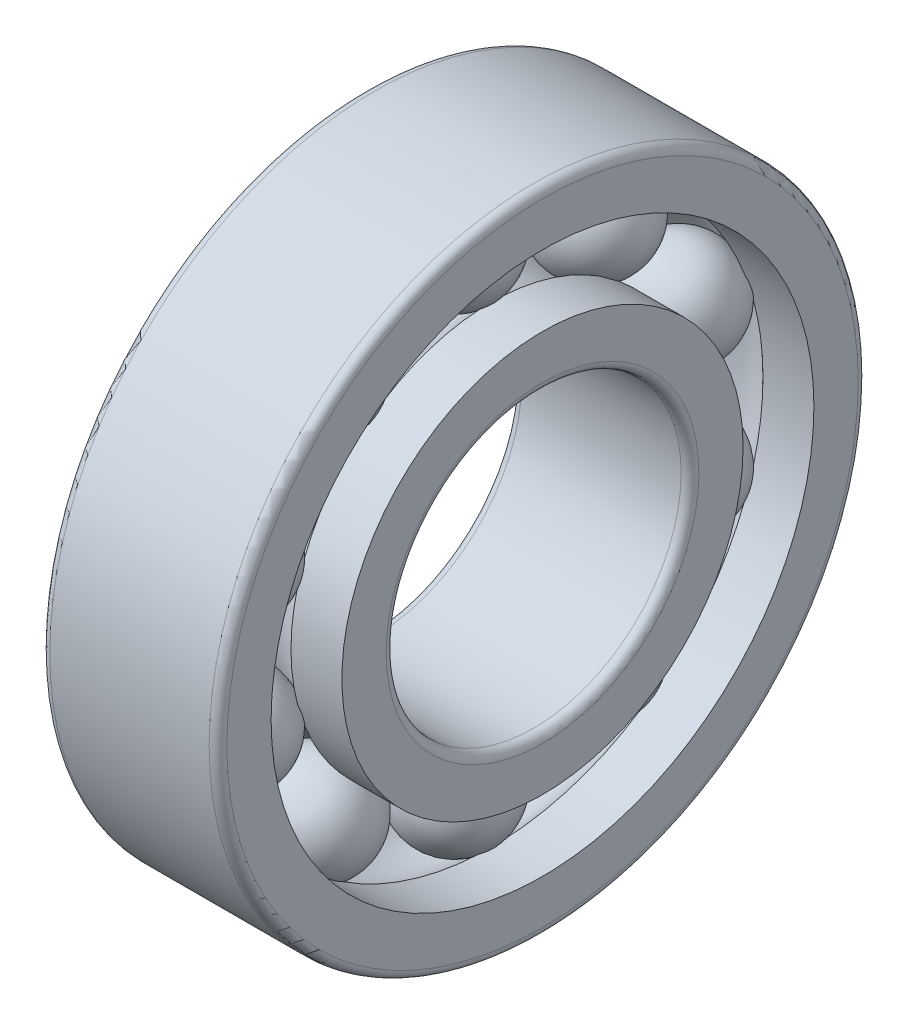
SolidWorks part; units mm, degrees
ref_plane "Plane1" through (0, 0, 0) normal (0, 0, 1) x (1, 0, 0)
ref_plane "Plane2" through (0, 0, 0) normal (0, 1, 0) x (1, 0, 0)
ref_plane "Plane3" through (0, 0, 0) normal (1, 0, 0) x (0, 0, -1)
sketch "Clipboard" plane through (0, 0, 0) normal (0, 0, 1) x (1, 0, 0)
  line L0 (-10, 0) -> (10, 0) construction
  line L1 (0, 0) -> (22.021, -3.8829)
  line L2 (0, 0) -> (3.9392, 0.6946)
  line L3 (0, 0) -> (22.021, -3.8829)
  line L4 (0, 0) -> (-22.3573, -0.3902)
  dimension "BallCLRad" = 4
sketch "CagSpiSke" plane through (0, 0, 0) normal (0, 0, 1) x (1, 0, 0)
  line L0 (0.09, 3.85) -> (0.09, 4.15)
  line L1 (0.09, 4.15) -> (-0.09, 4.15)
  line L2 (-0.09, 4.15) -> (-0.09, 3.85)
  line L3 (-0.09, 3.85) -> (0.09, 3.85)
  line L4 (-20.6375, 0) -> (20.6375, 0) construction
  line L5 (0, 0) -> (0, 23.7692) construction
  dimension "OD" = 8.3
  dimension "ID" = 7.7
revolve "CageSpine" add sketch "CagSpiSke" angle 0.001 about L4 reverse direction yes
ref_axis "Axis1" through (-50, 0, 0) along (1, 0, 0)
sketch "CagBalSke" plane through (0, 0, 0) normal (0, 0, 1) x (1, 0, 0)
  line L0 (-0.99, 4) -> (0.99, 4)
  line L1 (-1.905, 4) -> (1.905, 4) construction
  line L2 (-10, 0) -> (10, 0) construction
  line L3 (0, 0) -> (0, 24) construction
  arc A0 (0.99, 4) -> (-0.99, 4) centre (0, 4) cw
  dimension "BallCLRad" = 4
revolve "CageBall" [suppressed] add sketch "CagBalSke" angle 360 about L1 reverse direction yes
pattern_circular "CageBalls" [suppressed] count 10 every 36 about axis through (-50, 0, 0) along (1, 0, 0)
sketch "CagTrmODSke" plane through (0, 0, 0) normal (0, 0, 1) x (1, 0, 0)
  line L0 (0.991, 4.15) -> (0.991, 4.991)
  line L1 (0.991, 4.991) -> (-0.991, 4.991)
  line L2 (-0.991, 4.991) -> (-0.991, 4.15)
  line L3 (-0.991, 4.15) -> (0.991, 4.15)
  line L4 (-20.6375, 0) -> (20.6375, 0) construction
  line L5 (0, 0) -> (0, 25) construction
  dimension "Width" = 1.982
  dimension "ID" = 8.3
  dimension "OD" = 9.982
revolve "CageTrimOD" [suppressed] cut sketch "CagTrmODSke" angle 360 about L4 reverse direction yes
sketch "CagTrmIDSke" plane through (0, 0, 0) normal (0, 0, 1) x (1, 0, 0)
  line L0 (0.991, 3.011) -> (0.991, 3.85)
  line L1 (0.991, 3.85) -> (-0.991, 3.85)
  line L2 (-0.991, 3.85) -> (-0.991, 3.011)
  line L3 (-0.991, 3.011) -> (0.991, 3.011)
  line L4 (-20.6375, 0) -> (20.6375, 0) construction
  line L5 (0, 0) -> (0, 25) construction
  dimension "Width" = 1.982
  dimension "ID" = 6.022
  dimension "OD" = 7.7
revolve "CageTrimID" [suppressed] cut sketch "CagTrmIDSke" angle 360 about L4 reverse direction yes
sketch "BalSimSke" plane through (0, 0, 0) normal (0, 0, 1) x (1, 0, 0)
  line L0 (-10, 0) -> (10, 0) construction
  line L1 (-10, 4) -> (10, 4) construction
  line L2 (0, 0) -> (0, 23) construction
  circle A0 centre (0, 4) radius 0.9
  dimension "BallCLRad" = 4
  dimension "Ball_diameter" = 1.8
revolve "BallsSimplified" [suppressed] add sketch "BalSimSke" angle 360 about L0
sketch "BalDetSke" plane through (0, 0, 0) normal (0, 0, 1) x (1, 0, 0)
  line L0 (-0.9, 4) -> (0.9, 4)
  line L1 (-1.905, 4) -> (1.905, 4) construction
  line L2 (0, 0) -> (0, 25) construction
  arc A0 (0.9, 4) -> (-0.9, 4) centre (0, 4) cw
  dimension "BallCLRad" = 4
  dimension "Ball_diameter" = 1.8
revolve "BallDetailed" add sketch "BalDetSke" angle 360 about L1 reverse direction yes
sketch "InnRacSke" plane through (0, 0, 0) normal (0, 0, 1) x (1, 0, 0)
  line L0 (-0.6369, 3.4) -> (-1.5, 3.4)
  line L1 (-1.5, 3.4) -> (-1.5, 2.65)
  line L2 (-1.35, 2.5) -> (1.35, 2.5)
  line L3 (1.5, 2.65) -> (1.5, 3.4)
  line L4 (1.5, 3.4) -> (0.6369, 3.4)
  line L5 (-20.6375, 0) -> (20.6375, 0) construction
  line L6 (0, 0) -> (0, 30) construction
  arc A0 (-1.5, 2.65) -> (-1.35, 2.5) centre (-1.35, 2.65) ccw
  arc A1 (1.35, 2.5) -> (1.5, 2.65) centre (1.35, 2.65) ccw
  arc A2 (0.6369, 3.4) -> (-0.6369, 3.4) centre (0, 4) cw
  dimension "BallCLRad" = 4
  dimension "Fillet_radius" = 0.15
  dimension "Ball_diameter" = 1.75
  dimension "ID" = 5
  dimension "OD" = 6.8
  dimension "Width" = 3
revolve "InnerRace" add sketch "InnRacSke" angle 360 about L5 reverse direction yes
sketch "OutRacSke" plane through (0, 0, 0) normal (0, 0, 1) x (1, 0, 0)
  line L0 (-0.6369, 4.6) -> (-1.5, 4.6)
  line L1 (-1.5, 4.6) -> (-1.5, 5.35)
  line L2 (-1.35, 5.5) -> (1.35, 5.5)
  line L3 (1.5, 5.35) -> (1.5, 4.6)
  line L4 (1.5, 4.6) -> (0.6369, 4.6)
  line L5 (-20.6375, 0) -> (20.6375, 0) construction
  line L6 (0, 0) -> (0, 30) construction
  arc A0 (-1.5, 5.35) -> (-1.35, 5.5) centre (-1.35, 5.35) cw
  arc A1 (1.35, 5.5) -> (1.5, 5.35) centre (1.35, 5.35) cw
  arc A2 (0.6369, 4.6) -> (-0.6369, 4.6) centre (0, 4) ccw
  dimension "BallCLRad" = 4
  dimension "Fillet_radius" = 0.15
  dimension "Ball_diameter" = 1.75
  dimension "Width" = 3
revolve "OuterRace" add sketch "OutRacSke" angle 360 about L5 reverse direction yes
pattern_circular "BallsDetailed" count 10 every 36 about axis through (-50, 0, 0) along (1, 0, 0) of "BallDetailed"
equation "\"BallCLRad@Clipboard\" = ( \"OD@OutRacSke\" + \"ID@InnRacSke\" ) / 4"
equation "\"BallCLRad@BalSimSke\" = \"BallCLRad@Clipboard\""
equation "\"BallCLRad@BalDetSke\" = \"BallCLRad@Clipboard\""
equation "\"BallCLRad@InnRacSke\" = \"BallCLRad@Clipboard\""
equation "\"BallCLRad@OutRacSke\" = \"BallCLRad@Clipboard\""
equation "\"Ball_diameter@InnRacSke\" = \"Ball_diameter@BalDetSke\" - 0.05"
equation "\"Ball_diameter@OutRacSke\" = \"Ball_diameter@BalDetSke\" - 0.05"
equation "\"Ball_diameter@BalSimSke\" = \"Ball_diameter@BalDetSke\""
equation "\"Width@OutRacSke\" = \"Width@InnRacSke\""
equation "\"Fillet_radius@OutRacSke\" = \"Fillet_radius@InnRacSke\""
equation "\"Max_count@Clipboard\" = int( 3.14159265 / atn(( \"Ball_diameter@BalDetSke\" / 2) / sqr( \"BallCLRad@Clipboard\"  *  \"BallCLRad@Clipboard\" - ( \"Ball_diameter@BalDetSke\" / 2) *  ( \"Ball_diameter@BalDetSke\" / 2))))"
equation "\"Max_count@Clipboard\" = ((sgn( \"Max_count@Clipboard\" - \"Count@Clipboard\" )-1)*( \"Max_count@Clipboard\" - \"Count@Clipboard\" ))/-2+ \"Count@Clipboard\""
equation "\"Count@BallsDetailed\" = int( \"Show_count@Clipboard\" ) "
equation "\"Count@BallsDetailed\" = ((sgn( \"Count@BallsDetailed\" - \"Max_count@Clipboard\" )-1)*( \"Count@BallsDetailed\" - \"Max_count@Clipboard\" ))/-2+ \"Max_count@Clipboard\""
equation "\"Count@BallsDetailed\" = ((sgn( \"Count@BallsDetailed\" - \"Min_count@Clipboard\" )+1)*( \"Count@BallsDetailed\" - \"Min_count@Clipboard\"))/2 +\"Min_count@Clipboard\""
equation "\"Angle@BallsDetailed\" = 360.0 / \"Max_count@Clipboard\""
equation "\"BallCLRad@CagBalSke\" = \"BallCLRad@Clipboard\""
equation "\"Count@CageBalls\" = \"Count@BallsDetailed\""
equation "\"Angle@CageBalls\" = \"Angle@BallsDetailed\""
equation "\"Angle@CageSpine\" =  \"Angle@CageBalls\" * ( \"Count@CageBalls\" -1 + int( \"Count@CageBalls\" / \"Max_count@Clipboard\" ) )  + 0.001 -  int( \"Count@CageBalls\" / \"Max_count@Clipboard\" ) * 0.001"
equation "\"Angle@CageSpine\" =  \"Angle@CageSpine\" * int( \"Min_count@Clipboard\" / 2) + int(1 / \"Min_count@Clipboard\")  * 0.001"
equation "\"CageWallOD@CagBalSke\" =  \"Ball_diameter@BalDetSke\" * 1.1"
equation "\"Thickness@CagSpiSke\" =  \"Ball_diameter@BalDetSke\" * 0.1"
equation "\"OD@CagTrmODSke\" = \"BallCLRad@Clipboard\" * 2 + \"CageWallOD@CagBalSke\" + 0.002"
equation "\"ID@CagTrmODSke\" = \"BallCLRad@Clipboard\" * 2 + \"Ball_diameter@BalDetSke\" / 6"
equation "\"OD@CagTrmIDSke\" = \"BallCLRad@Clipboard\" * 2 - \"Ball_diameter@BalDetSke\" / 6"
equation "\"ID@CagTrmIDSke\" = \"BallCLRad@Clipboard\" * 2 - \"CageWallOD@CagBalSke\" + 0.002"
equation "\"OD@CagSpiSke\" = \"ID@CagTrmODSke\""
equation "\"ID@CagSpiSke\" = \"OD@CagTrmIDSke\""
equation "\"Width@CagTrmODSke\" = \"CageWallOD@CagBalSke\" + 0.002"
equation "\"Width@CagTrmIDSke\" = \"CageWallOD@CagBalSke\" + 0.002"
